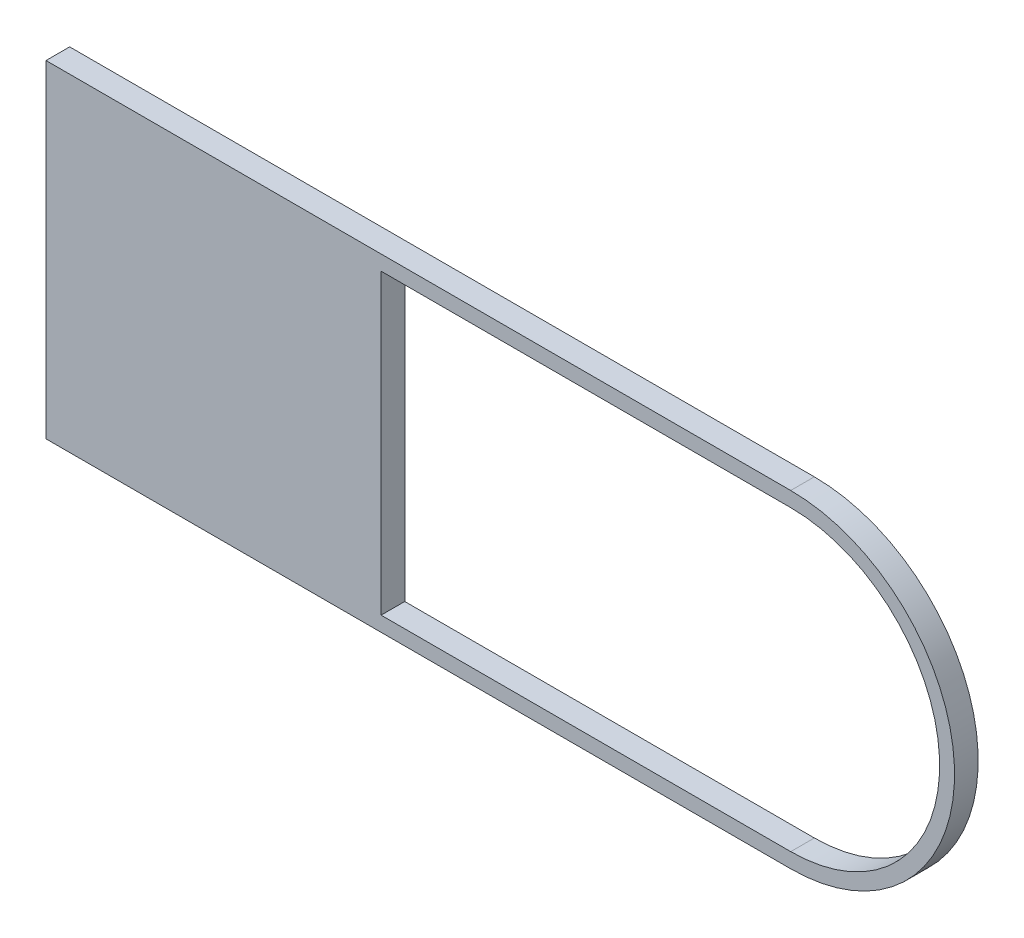
SolidWorks part; units mm, degrees
ref_plane "Front Plane" through (0, 0, 0) normal (0, 0, 1) x (1, 0, 0)
ref_plane "Top Plane" through (0, 0, 0) normal (0, 1, 0) x (1, 0, 0)
ref_plane "Right Plane" through (0, 0, 0) normal (1, 0, 0) x (0, 0, -1)
sketch "Sketch1" plane through (0, 0, 0) normal (0, 0, 1) x (1, 0, 0)
  line L3 (0, 0) -> (100, 0)
  line L4 (0, 0) -> (0, 44)
  line L5 (0, 44) -> (100, 44)
  line L6 (45, 2) -> (45, 42)
  line L7 (45, 42) -> (100, 42)
  line L8 (45, 2) -> (100, 2)
  arc A1 (100, 44) -> (100, 0) centre (100, 22) cw
  arc A2 (100, 2) -> (100, 42) centre (100, 22) ccw
  point P12 (0, 0)
  point P13 (120, 22)
  dimension "D1" = 20
  dimension "D2" = 2
  dimension "D3" = 2
  dimension "D4" = 45
  dimension "D5" = 120
extrude "Boss-Extrude1" add sketch "Sketch1" along normal blind 3.175
